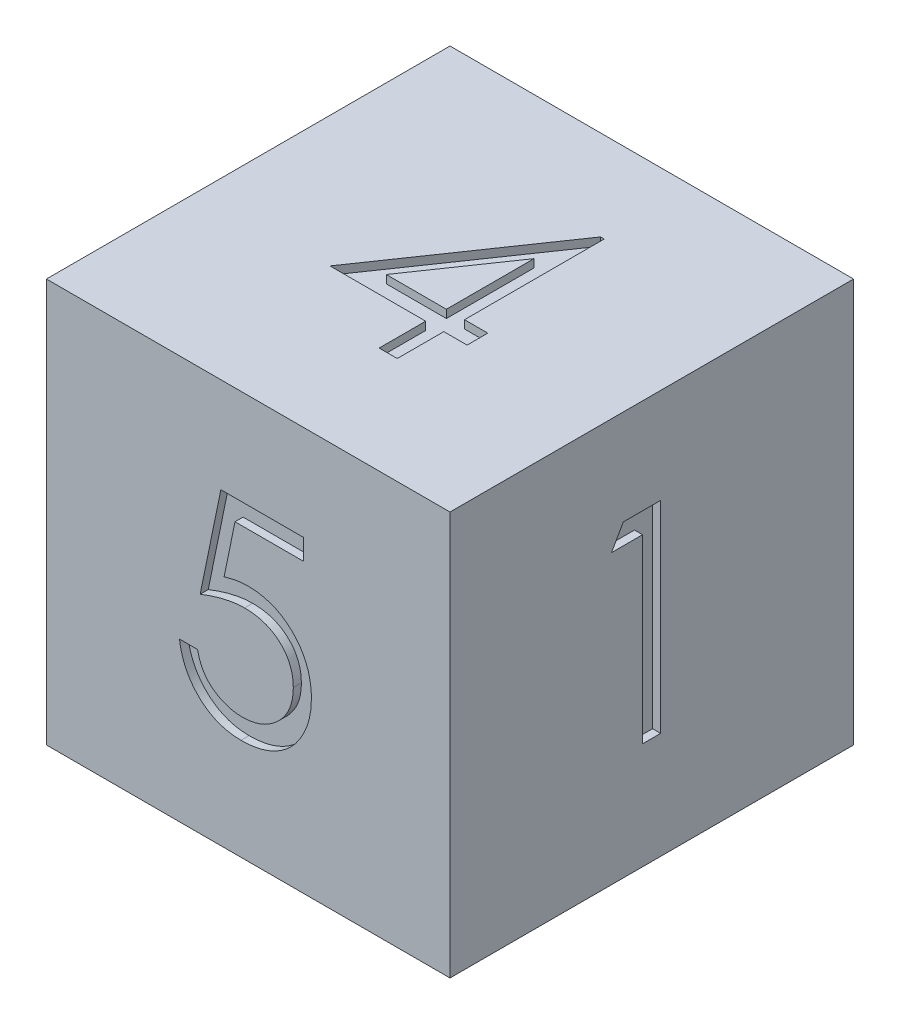
SolidWorks part; units mm, degrees
ref_plane "Front Plane" through (0, 0, 0) normal (0, 0, 1) x (1, 0, 0)
ref_plane "Top Plane" through (0, 0, 0) normal (0, 1, 0) x (1, 0, 0)
ref_plane "Right Plane" through (0, 0, 0) normal (1, 0, 0) x (0, 0, -1)
sketch "Sketch1" plane through (0, 0, 0) normal (0, 0, 1) x (1, 0, 0)
  line L1 (-25, 25) -> (25, 25)
  line L2 (-25, 25) -> (-25, -25)
  line L3 (-25, -25) -> (25, -25)
  line L4 (25, 25) -> (25, -25)
  line L5 (-25, 25) -> (25, -25) construction
  line L6 (-25, -25) -> (25, 25) construction
  point P0 (0, 0)
  dimension "D1" = 50
  dimension "D2" = 50
extrude "Boss-Extrude1" add sketch "Sketch1" along normal blind 25 and the other way blind 25
sketch "Sketch2" plane through (25, 0, 0) normal (1, 0, 0) x (0, 0, -1)
  text T0 "1" font "Century Gothic" height 25
  point P1 (-4.8909, -7.768)
  point P2 (-8.0557, -10.7888)
  point P3 (0, 0)
  point P4 (0, 0)
  point P5 (-9.9976, -12.0835)
  point P6 (0, 0)
extrude "Cut-Extrude1" cut sketch "Sketch2" against normal blind 1
sketch "Sketch3" plane through (-25, 0, 0) normal (-1, 0, 0) x (0, 0, 1)
  text T0 "6" font "Century Gothic" height 25
  point P1 (-6.4134, -9.5901)
extrude "Cut-Extrude2" cut sketch "Sketch3" against normal blind 1
sketch "Sketch4" plane through (0, 0, 25) normal (0, 0, 1) x (1, 0, 0)
  text T0 "5" font "Century Gothic" height 25
  point P1 (0, 0)
extrude "Cut-Extrude3" cut sketch "Sketch4" against normal blind 1
sketch "Sketch5" plane through (0, 0, -25) normal (0, 0, -1) x (-1, 0, 0)
  text T0 "2" font "Century Gothic" height 25
  point P1 (0, 0)
extrude "Cut-Extrude4" cut sketch "Sketch5" against normal blind 1
sketch "Sketch6" plane through (0, 25, 0) normal (0, 1, 0) x (1, 0, 0)
  text T0 "4" font "Century Gothic" height 25
  point P1 (0, 0)
extrude "Cut-Extrude5" cut sketch "Sketch6" against normal blind 1
sketch "Sketch7" plane through (0, -25, 0) normal (0, -1, 0) x (1, 0, 0)
  text T0 "3" font "Century Gothic" height 25
  point P1 (0, 0)
extrude "Cut-Extrude6" cut sketch "Sketch7" against normal blind 1
